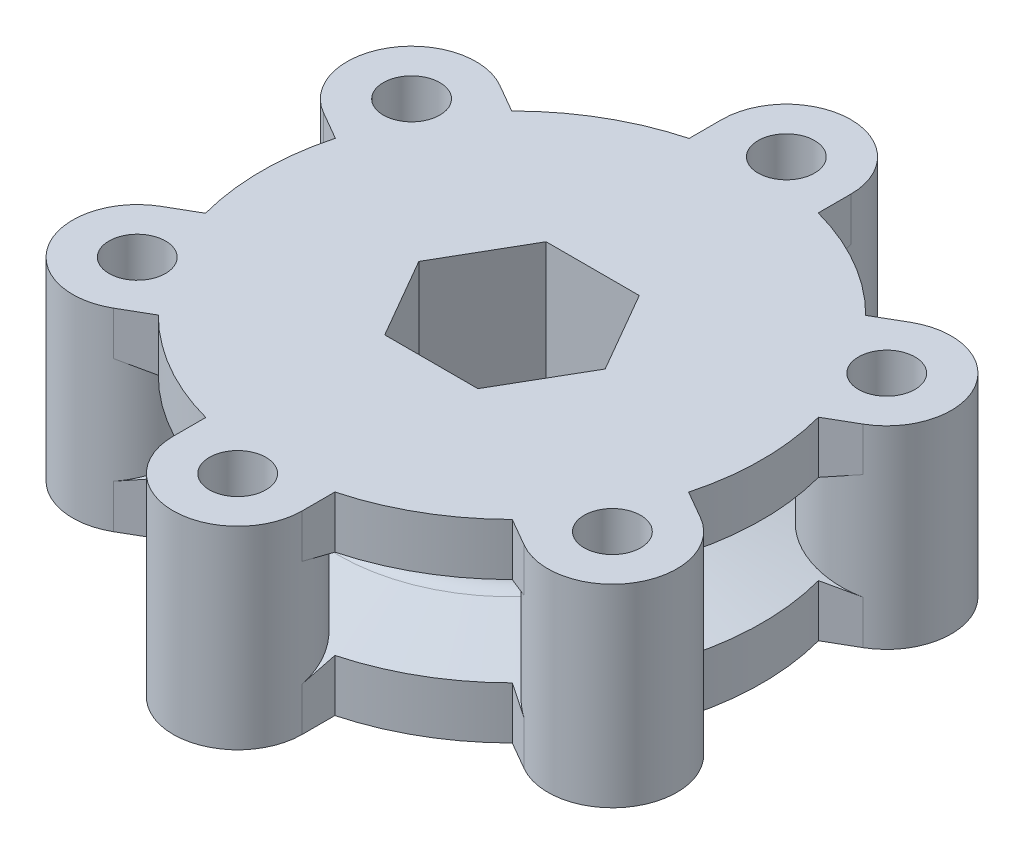
SolidWorks part; units mm, degrees
material "PLA/ABS"
ref_plane "Front Plane" through (0, 0, 0) normal (0, 0, 1) x (1, 0, 0)
ref_plane "Top Plane" through (0, 0, 0) normal (0, 1, 0) x (1, 0, 0)
ref_plane "Right Plane" through (0, 0, 0) normal (1, 0, 0) x (0, 0, -1)
other "Bounding Box"
ref_plane "Default Plane" through (13.8565, 3.175, 6.7999) normal (0, -1, 0) x (-1, 0, 0)
sketch "Sketch1" plane through (0, 0, 0) normal (0, 1, 0) x (1, 0, 0)
  line L0 (22.4506, -22.4506) -> (0, 0) construction
  line L1 (0, 0) -> (22.4506, 22.4506) construction
  line L2 (0, 0) -> (0, 31.75) construction
  circle A0 centre (0, 0) radius 31.75
  point P3 (0, 31.75)
  point P4 (31.75, 0)
  point P5 (-31.75, 0)
  point P6 (0, -31.75)
  point P7 (22.4506, 22.4506)
  point P8 (22.4506, -22.4506)
  dimension "D1" = 63.5
  dimension "D2" = 45
extrude "Boss-Extrude1" add sketch "Sketch1" along normal mid plane 15.24
ref_plane "Plane2" through (-31.75, 0, 0) normal (-1, 0, 0) x (0, 0, 1)
sketch "Sketch9" plane through (-31.75, 0, 0) normal (-1, 0, 0) x (0, 0, 1)
  line L0 (-0.635, -7.62) -> (0.635, -7.62)
  line L1 (-31.75, -7.62) -> (31.75, -7.62) construction
  line L2 (0.635, -7.62) -> (0.635, 0)
  line L3 (31.75, 7.62) -> (-31.75, 7.62) construction
  line L5 (-0.635, 0) -> (-0.635, -7.62)
  line L6 (0.635, -7.62) -> (0, -7.62) construction
  line L7 (0, -7.62) -> (0, 7.62) construction
  line L9 (-0.635, 0) -> (0.635, 0) construction
  line L10 (0.635, 0) -> (0.635, 7.62)
  line L11 (0.635, 7.62) -> (-0.635, 7.62)
  line L13 (-0.635, 7.62) -> (-0.635, 0)
  point P14 (0, 0)
  dimension "D2" = 1.27
extrude "Cut-Extrude4" cut sketch "Sketch9" against normal blind 0.635
sketch "Sketch4" plane through (0, 0, 0) normal (0, 0, 1) x (1, 0, 0)
  line L0 (-31.75, -7.62) -> (-29.21, -7.62)
  line L1 (-31.7436, -7.62) -> (31.75, -7.62) construction
  line L4 (31.75, 7.62) -> (-31.7436, 7.62) construction
  line L5 (-29.21, 7.62) -> (-31.75, 7.62)
  line L6 (-31.75, 7.62) -> (-31.75, -7.62)
  line L7 (-6.35, 0) -> (0, 0) construction
  line L8 (-29.21, -7.62) -> (-29.21, -6.0325)
  line L9 (-29.21, -6.0325) -> (-6.35, 0)
  line L10 (-6.35, 0) -> (-29.21, 6.0325)
  line L11 (-29.21, 6.0325) -> (-29.21, 7.62)
  point P17 (-31.75, 0)
  dimension "D1" = 2.54
  dimension "D2" = 25.4
  dimension "D3" = 1.5875
pattern_circular "CirPattern2" count 20 over 360 about axis through (0, -7.62, 0) along (0, 1, 0) of "Cut-Extrude4"
ref_axis "Axis1" through (0, -9.0805, 0) along (0, 1, 0)
sketch "Sketch3" plane through (0, 7.62, 0) normal (0, 1, 0) x (1, 0, 0)
  line L0 (0, 0) -> (0, 21.59) construction
  line L1 (0, 21.59) -> (0, 31.75) construction
  circle A0 centre (0, 21.59) radius 2.2225
  circle A1 centre (0, 0) radius 31.75 construction
  circle A2 centre (0, 21.59) radius 5.08
  dimension "D2" = 4.445
  dimension "D3" = 10.16
  dimension "D1" = 10.16
move or copy body "Body-Move/Copy1" [suppressed] parameters "D1"=0, "D2"=0, "D3"=0
revolve "Cut-Revolve2" cut sketch "Sketch4" angle 360 about axis through (0, -9.0805, 0) along (0, 1, 0)
sketch "Sketch5" plane through (0, 7.62, 0) normal (0, 1, 0) x (1, 0, 0)
  circle A0 centre (0, 21.59) radius 5.08
  circle A1 centre (0, 21.59) radius 2.2225 construction
  circle A3 centre (0, 21.59) radius 2.2225
  circle A4 centre (0, 21.59) radius 5.08 construction
extrude "Boss-Extrude2" add sketch "Sketch5" against normal through all
sketch "Sketch12" plane through (0, 7.62, 0) normal (0, 1, 0) x (1, 0, 0)
  line L0 (-18.6975, 10.795) -> (0, 0) construction
  line L1 (-18.6975, -10.795) -> (-18.6975, 10.795) construction
  line L2 (-18.6975, 10.795) -> (0, 21.59) construction
  line L3 (-18.6975, -10.795) -> (0, 0) construction
  line L4 (0, 0) -> (0, 21.59) construction
  circle A0 centre (-18.6975, 10.795) radius 5.08
  circle A1 centre (0, 21.59) radius 5.08 construction
  dimension "D3" = 120
extrude "Boss-Extrude6" add sketch "Sketch12" against normal through all
sketch "Sketch17" plane through (0, 0, 0) normal (0, 1, 0) x (1, 0, 0)
  line L0 (0, 21.59) -> (0, 0) construction
  line L1 (0, 0) -> (-18.6975, 10.795) construction
  line L2 (0, 0) -> (-18.6975, -10.795) construction
  line L3 (-23.0969, -13.335) -> (-25.2966, -14.605)
  line L4 (0, 26.67) -> (0, 29.21)
  line L5 (-21.2375, -6.3956) -> (-19.0103, -5.1097)
  line L6 (-19.0103, 5.1097) -> (-21.2375, 6.3956)
  line L7 (-16.1575, 15.1944) -> (-13.9303, 13.9085)
  line L8 (-5.08, 21.59) -> (-5.08, 19.0182)
  circle A0 centre (0, 21.59) radius 5.08 construction
  circle A1 centre (-18.6975, 10.795) radius 5.08 construction
  arc A2 (0, 26.67) -> (-5.08, 21.59) centre (0, 21.59) ccw
  arc A3 (-16.1575, 15.1944) -> (-21.2375, 6.3956) centre (-18.6975, 10.795) ccw
  arc A5 (-5.08, 19.0182) -> (-13.9303, 13.9085) centre (0, 0) ccw
  circle A6 centre (0, 21.59) radius 2.2225 construction
  arc A7 (-21.2375, -6.3956) -> (-23.0969, -13.335) centre (-18.6975, -10.795) ccw
  circle A8 centre (0, 0) radius 29.21 construction
  circle A9 centre (0, 21.59) radius 2.2225
  circle A10 centre (0, 0) radius 29.21 construction
  arc A11 (0, 29.21) -> (-25.2966, -14.605) centre (0, 0) ccw
  arc A12 (-19.0103, 5.1097) -> (-19.0103, -5.1097) centre (0, 0) ccw
  circle A13 centre (-18.6975, 10.795) radius 2.2225
  circle A15 centre (-18.6975, -10.795) radius 2.2225
  dimension "D1" = 9.525
extrude "Cut-Extrude5" cut sketch "Sketch17" against normal through all both and the other way through all
pattern_circular "CirPattern1" count 3 over 360 about axis through (0, 6.0325, 0) along (0, -1, 0) of "Boss-Extrude2", "Boss-Extrude6", "Cut-Extrude5"
sketch "Sketch18" plane through (0, -7.62, 0) normal (0, -1, 0) x (1, 0, 0)
  circle A0 centre (0, 0) radius 19.685 construction
  circle A1 centre (0, 0) radius 12.7
  arc A2 (-5.08, 19.0182) -> (-13.9303, 13.9085) centre (0, 0) ccw construction
  circle A3 centre (0, 0) radius 6.35 construction
  circle A4 centre (0, 0) radius 6.35 construction
  circle A5 centre (0, 0) radius 31.75 construction
  dimension "D1" = 19.05
extrude "Boss-Extrude9" add sketch "Sketch18" against normal through all
fillet "Fillet5" radius 1.27 2 edges at (0, -1.6757, -12.7) (0, 1.6757, 12.7)
sketch "Sketch24" plane through (0, -7.62, 0) normal (0, -1, 0) x (1, 0, 0)
  line L1 (3.6662, -6.35) -> (7.3323, 0)
  line L2 (7.3323, 0) -> (3.6662, 6.35)
  line L3 (3.6662, 6.35) -> (-3.6662, 6.35)
  line L4 (-3.6662, 6.35) -> (-7.3323, 0)
  line L5 (-7.3323, 0) -> (-3.6662, -6.35)
  line L6 (-3.6662, -6.35) -> (3.6662, -6.35)
  circle A0 centre (0, 0) radius 4 construction
  circle A1 centre (0, 0) radius 6.35 construction
  dimension "D1" = 8
  dimension "D2" = 12.7
extrude "Cut-Extrude7" cut sketch "Sketch24" against normal through all
combine bodies "Combine3" [suppressed] bodies to combine 116 167
delete or keep bodies "Body-Delete/Keep 4" [suppressed] type keep bodies bodies 117
sketch "Sketch7" [suppressed] plane through (0, -8.255, 0) normal (0, -1, 0) x (1, 0, 0)
  circle A0 centre (0, 0) radius 44.45
  circle A1 centre (0, 0) radius 38.1 construction
  dimension "D1" = 6.35
extrude "Boss-Extrude4" [suppressed] add sketch "Sketch7" against normal offset from surface (19.685 mm away) 3.175 separate body offset beyond the face yes
combine bodies "Combine2" [suppressed] operation type add bodies to combine 110 114
sketch "Sketch15" [suppressed] plane through (0, 0, 0) normal (1, 0, 0) x (0, 0, -1)
  line L0 (-38.1, -8.255) -> (-43.18, -13.335)
  line L1 (-43.18, -13.335) -> (-36.83, -13.335)
  line L2 (-36.83, -13.335) -> (-31.75, -8.255)
  line L3 (-31.75, -8.255) -> (-38.1, -8.255)
  dimension "D1" = 5.08
  dimension "D2" = 45
  dimension "D3" = 6.35
ref_axis "Axis2" [suppressed] through (0, -9.0805, 0) along (0, 1, 0)
revolve "Revolve1" [suppressed] add sketch "Sketch15" angle 360 about axis through (0, -9.0805, 0) along (0, 1, 0)
fillet "Fillet4" [suppressed] radius 6.35
sketch "Sketch27" [suppressed] plane through (0, 11.43, 0) normal (0, 1, 0) x (1, 0, 0)
  line L0 (37.5671, 6.35) -> (44.45, 6.35)
  line L1 (44.45, -6.35) -> (37.5671, -6.35)
  line L2 (38.1, 0) -> (44.45, 0) construction
  circle A0 centre (44.45, 0) radius 1.905
  arc A1 (37.5671, -6.35) -> (37.5671, 6.35) centre (0, 0) ccw
  circle A2 centre (0, 0) radius 38.1 construction
  arc A3 (44.45, 6.35) -> (44.45, -6.35) centre (44.45, 0) cw
  dimension "D2" = 3.81
  dimension "D3" = 6.35
  dimension "D1" = 6.35
extrude "Boss-Extrude13" [suppressed] add sketch "Sketch27" against normal blind 9.525
pattern_circular "CirPattern7" [suppressed] count 3 over 360 of bodies 177
split "Split1" [suppressed] bodies to split 124
sketch "Sketch19" [suppressed] plane through (0, 11.43, 0) normal (0, 1, 0) x (1, 0, 0)
  line L0 (-20.447, 35.4152) -> (-19.177, 33.2155)
  line L1 (-20.447, -35.4152) -> (-19.177, -33.2155)
  line L2 (-40.894, 0) -> (0, 0) construction
  arc A0 (-19.177, 33.2155) -> (-19.177, -33.2155) centre (0, 0) ccw
  circle A1 centre (0, 0) radius 38.1 construction
  arc A2 (-20.447, 35.4152) -> (-20.447, -35.4152) centre (0, 0) ccw
  dimension "D2" = 2.54
  dimension "D3" = 0.254
  dimension "D1" = 120
extrude "Boss-Extrude10" [suppressed] add sketch "Sketch19" against normal blind 6.35 separate body
sketch "Sketch21" [suppressed] plane through (0, 11.43, 0) normal (0, 1, 0) x (1, 0, 0)
  line L0 (-19.177, 33.2155) -> (-19.05, 32.9956)
  line L1 (-19.177, -33.2155) -> (-19.05, -32.9956)
  line L2 (-19.177, 33.2155) -> (-20.447, 35.4152) construction
  line L3 (-20.447, -35.4152) -> (-19.177, -33.2155) construction
  arc A1 (-19.177, 33.2155) -> (-19.177, -33.2155) centre (0, 0) ccw construction
  arc A2 (-19.05, 32.9956) -> (-19.05, -32.9956) centre (0, 0) ccw
  arc A3 (-19.177, 33.2155) -> (-19.177, -33.2155) centre (0, 0) ccw
  circle A4 centre (0, 0) radius 38.1 construction
extrude "Boss-Extrude11" [suppressed] add sketch "Sketch21" against normal blind 3.1496
pattern_circular "CirPattern6" [suppressed] count 3 over 360 reverse direction yes of bodies 137 132
combine bodies "Combine4" [suppressed] bodies to combine 137 137 135 134
chamfer "Chamfer4" [suppressed] distance 0.635 angle 45
delete or keep bodies "Body-Delete/Keep 1" [suppressed] type delete bodies bodies 133
delete or keep bodies "Body-Delete/Keep 2" [suppressed] type delete bodies bodies 121
mirror "Mirror1" [suppressed] about plane through (0, 0, 0) normal (1, 0, 0) of bodies 121
delete or keep bodies "Body-Delete/Keep 3" [suppressed] type delete bodies bodies 121
sketch "Sketch28" [suppressed] plane through (0, 8.255, 0) normal (0, -1, 0) x (1, 0, 0)
  circle A0 centre (0, 0) radius 15.24
  dimension "D1" = 30.48
extrude "Boss-Extrude14" [suppressed] add sketch "Sketch28" along normal blind 0.635
sketch "Sketch29" [suppressed] plane through (0, 7.62, 0) normal (0, -1, 0) x (1, 0, 0)
  circle A0 centre (0, 0) radius 9.144
  dimension "D1" = 18.288
extrude "Boss-Extrude15" [suppressed] add sketch "Sketch29" along normal blind 10.16
sketch "Sketch30" [suppressed] plane through (0, -8.255, 0) normal (0, -1, 0) x (1, 0, 0)
  circle A12 centre (0, 0) radius 30.48
  circle A13 centre (0, 0) radius 27.94
  circle A14 centre (0, 0) radius 31.75 construction
  dimension "D1" = 1.27
  dimension "D2" = 2.54
extrude "Boss-Extrude16" [suppressed] add sketch "Sketch30" along normal blind 1.6002 separate body
sketch "Sketch31" [suppressed] plane through (0, -9.8552, 0) normal (0, -1, 0) x (1, 0, 0)
  line L0 (-5.9055, 21.59) -> (-5.9055, 29.9024)
  line L1 (-5.9055, 29.9024) -> (5.9055, 29.9024)
  line L2 (5.9055, 29.9024) -> (5.9055, 21.59)
  line L3 (0, 0) -> (0, 21.59) construction
  line L5 (-1.5875, 15.9019) -> (1.5875, 15.9019) construction
  line L6 (-1.5875, 15.9019) -> (-1.5875, 7.62)
  line L7 (-1.5875, 7.62) -> (1.5875, 7.62)
  line L8 (1.5875, 15.9019) -> (1.5875, 7.62)
  line L9 (-1.5875, 15.9019) -> (1.5875, 7.62) construction
  line L10 (-1.5875, 7.62) -> (1.5875, 15.9019) construction
  arc A0 (-1.5875, 15.9019) -> (-5.9055, 21.59) centre (0, 21.59) cw
  circle A1 centre (0, 21.59) radius 2.7305
  arc A2 (5.9055, 21.59) -> (1.5875, 15.9019) centre (0, 21.59) cw
  circle A3 centre (0, 21.59) radius 2.2225 construction
  circle A4 centre (0, 0) radius 30.48 construction
  point P6 (0, 11.7609)
  dimension "D1" = 3.175
  dimension "D2" = 5.461
  dimension "D3" = 7.62
  dimension "D4" = 3.175
extrude "Boss-Extrude17" [suppressed] add sketch "Sketch31" against normal up to surface (1.6002 mm away)
fillet "Fillet6" [suppressed] radius 2.54
pattern_circular "CirPattern8" [suppressed] count 6 over 360 of bodies 182
sketch "Sketch32" [suppressed] plane through (0, -9.8552, 0) normal (0, -1, 0) x (1, 0, 0)
  line L0 (0, 0) -> (-2.3034, 32.9396) construction
  line L1 (2.3034, 32.9396) -> (0.3104, 30.4784)
  line L2 (0, 0) -> (0, 33.02) construction
  line L3 (-1.8597, 30.4232) -> (-2.3034, 32.9396)
  line L4 (-2.3034, 32.9396) -> (-0.3104, 30.4784)
  line L5 (-0.3104, 30.4784) -> (-1.8597, 30.4232)
  line L6 (1.8597, 30.4232) -> (2.3034, 32.9396)
  line L7 (0.3104, 30.4784) -> (1.8597, 30.4232)
  circle A0 centre (0, 0) radius 30.48 construction
  circle A1 centre (0, 0) radius 33.02 construction
  circle A2 centre (0, 0) radius 31.75 construction
  dimension "D2" = 1.27
  dimension "D1" = 6
  dimension "D3" = 35
  dimension "D4" = 4
extrude "Boss-Extrude18" [suppressed] add sketch "Sketch32" against normal up to surface (1.6002 mm away)
fillet "Fillet7" [suppressed] radius 0.635
pattern_circular "CirPattern9" [suppressed] count 10 over 360 of bodies 184
delete or keep bodies "Body-Delete/Keep 5" [suppressed] bodies 185
sketch "Sketch33" [suppressed] plane through (0, -9.8552, 0) normal (0, -1, 0) x (1, 0, 0)
  line L1 (3.7028, -6.4135) -> (7.4057, 0)
  line L2 (7.4057, 0) -> (3.7028, 6.4135)
  line L3 (3.7028, 6.4135) -> (-3.7028, 6.4135)
  line L4 (-3.7028, 6.4135) -> (-7.4057, 0)
  line L5 (-7.4057, 0) -> (-3.7028, -6.4135)
  line L6 (-3.7028, -6.4135) -> (3.7028, -6.4135)
  circle A0 centre (0, 0) radius 6.4135 construction
  circle A1 centre (0, 0) radius 9.525
  dimension "D2" = 19.05
  dimension "D1" = 12.827
extrude "Boss-Extrude19" [suppressed] add sketch "Sketch33" against normal up to surface (1.6002 mm away)
